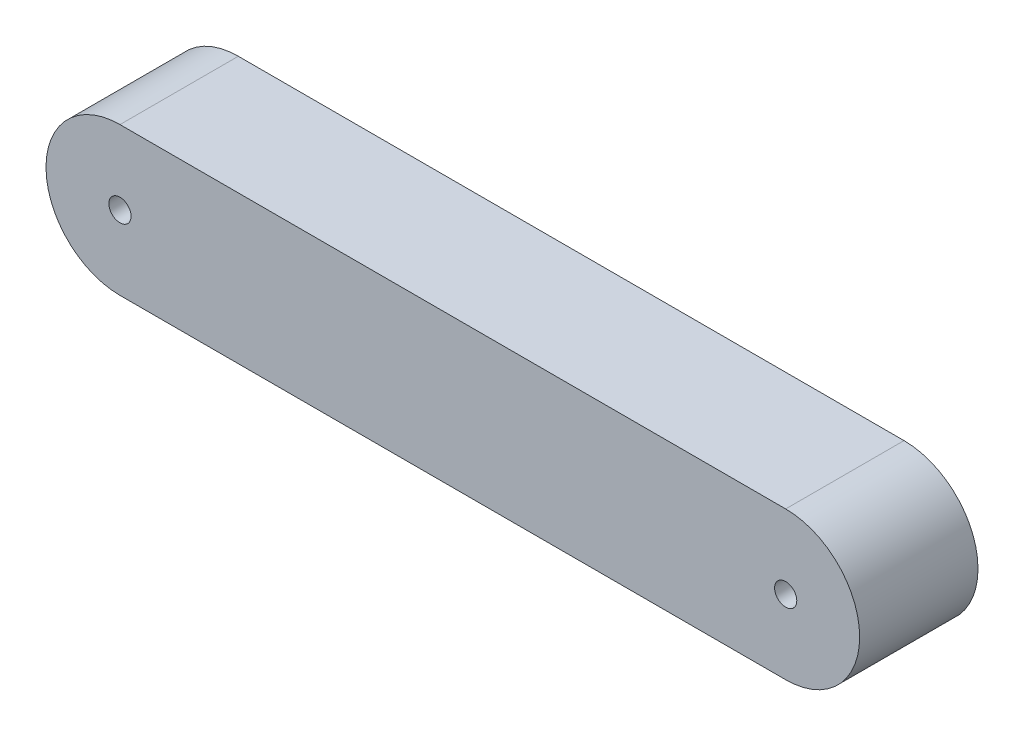
SolidWorks part; units mm, degrees
ref_plane "Front Plane" through (0, 0, 0) normal (0, 0, 1) x (1, 0, 0)
ref_plane "Top Plane" through (0, 0, 0) normal (0, 1, 0) x (1, 0, 0)
ref_plane "Right Plane" through (0, 0, 0) normal (1, 0, 0) x (0, 0, -1)
sketch "Sketch1" plane through (0, 0, 0) normal (0, 0, 1) x (1, 0, 0)
  line L1 (-3.7451, 2.0995) -> (86.2549, 2.0995)
  line L2 (-3.7451, 2.0995) -> (-3.7451, -17.9005)
  line L3 (-3.7451, -17.9005) -> (86.2549, -17.9005)
  line L4 (86.2549, 2.0995) -> (86.2549, -17.9005)
  arc A0 (-3.7451, 2.0995) -> (-3.7451, -17.9005) centre (-3.7451, -7.9005) ccw
  arc A1 (86.2549, 2.0995) -> (86.2549, -17.9005) centre (86.2549, -7.9005) cw
  dimension "D1" = 90
  dimension "D2" = 20
extrude "Boss-Extrude2" add sketch "Sketch1" along normal blind 16 contours L2 A0 | L4 L1 L2 L3 | A1 L4 region at (41.2549, -7.9005, 0) region at (-7.9893, -7.9005, 0) region at (90.499, -7.9005, 0)
sketch "Sketch2" plane through (0, 0, 16) normal (0, 0, 1) x (1, 0, 0)
  circle A0 centre (-3.7451, -7.9005) radius 1.5
  circle A1 centre (86.2549, -7.9005) radius 1.5
extrude "Cut-Extrude1" cut sketch "Sketch2" against normal blind 16
